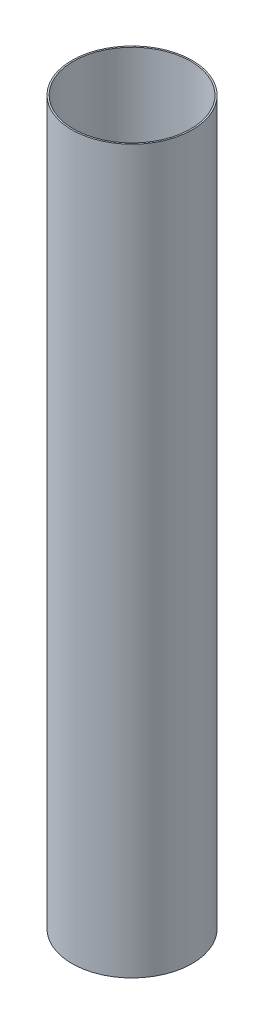
SolidWorks part; units mm, degrees
material "Wildman Fiberglass"
ref_plane "Front Plane" through (0, 0, 0) normal (0, 0, 1) x (1, 0, 0)
ref_plane "Top Plane" through (0, 0, 0) normal (0, 1, 0) x (1, 0, 0)
ref_plane "Right Plane" through (0, 0, 0) normal (1, 0, 0) x (0, 0, -1)
sketch "Sketch1" plane through (0, 0, 0) normal (0, 1, 0) x (1, 0, 0)
  circle A0 centre (0, 0) radius 49.53
  circle A1 centre (0, 0) radius 50.8
  dimension "D1" = 101.6
  dimension "D2" = 99.06
extrude "Boss-Extrude1" add sketch "Sketch1" along normal blind 609.6
equation "\"Length\"=24"
equation "\"D1@Boss-Extrude1\"=\"Length\""
